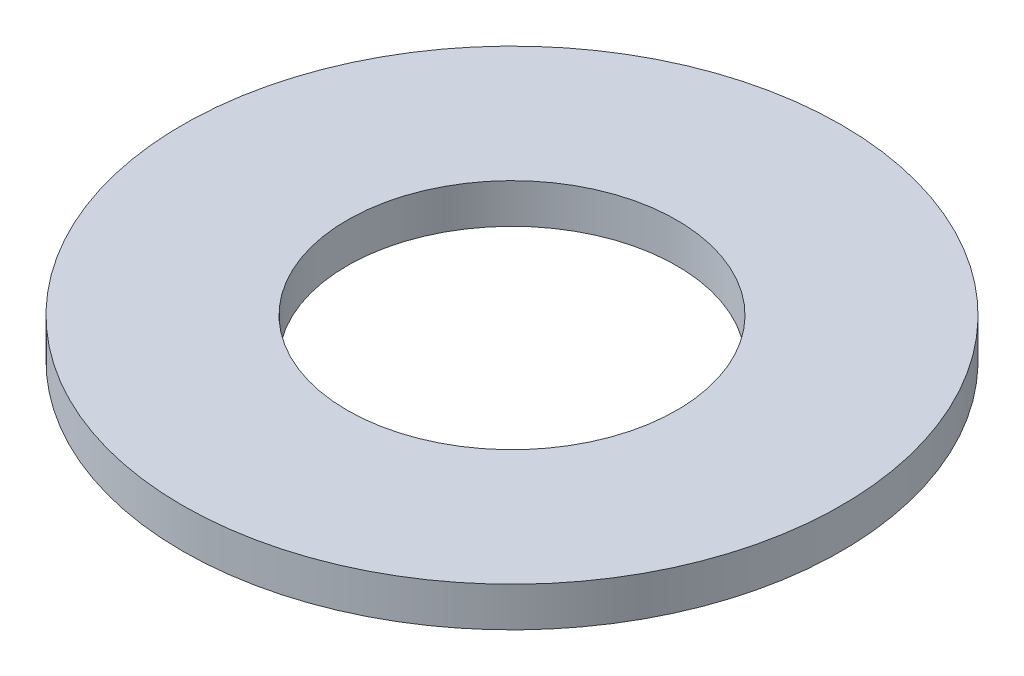
SolidWorks part; units mm, degrees
ref_plane "Front Plane" through (0, 0, 0) normal (0, 0, 1) x (1, 0, 0)
ref_plane "Top Plane" through (0, 0, 0) normal (0, 1, 0) x (1, 0, 0)
ref_plane "Right Plane" through (0, 0, 0) normal (1, 0, 0) x (0, 0, -1)
sketch "Sketch1" plane through (0, 0, 0) normal (0, 1, 0) x (1, 0, 0)
  circle A0 centre (0, 0) radius 75
  dimension "FLANGE_OD" = 150
extrude "Boss-Extrude1" add sketch "Sketch1" along normal blind 9
sketch "Sketch2" plane through (0, 0, 0) normal (0, 1, 0) x (1, 0, 0)
  circle A0 centre (0, 0) radius 37.5
  dimension "BORE_D" = 75
extrude "Cut-Extrude1" cut sketch "Sketch2" along normal through all
sketch "Sketch3" plane through (0, 9, 0) normal (0, 1, 0) x (1, 0, 0)
  circle A0 centre (0, 0) radius 27.2627 construction
  circle A1 centre (-27.2627, 0) radius 4.6505
  dimension "BOLT_D" = 9.301
  dimension "BOLT_PCD" = 54.5254
extrude "Cut-Extrude2" cut sketch "Sketch3" against normal blind 5.7572 rebuild error yes
pattern_circular "CirPattern1" count 8 over 360 rebuild error yes
